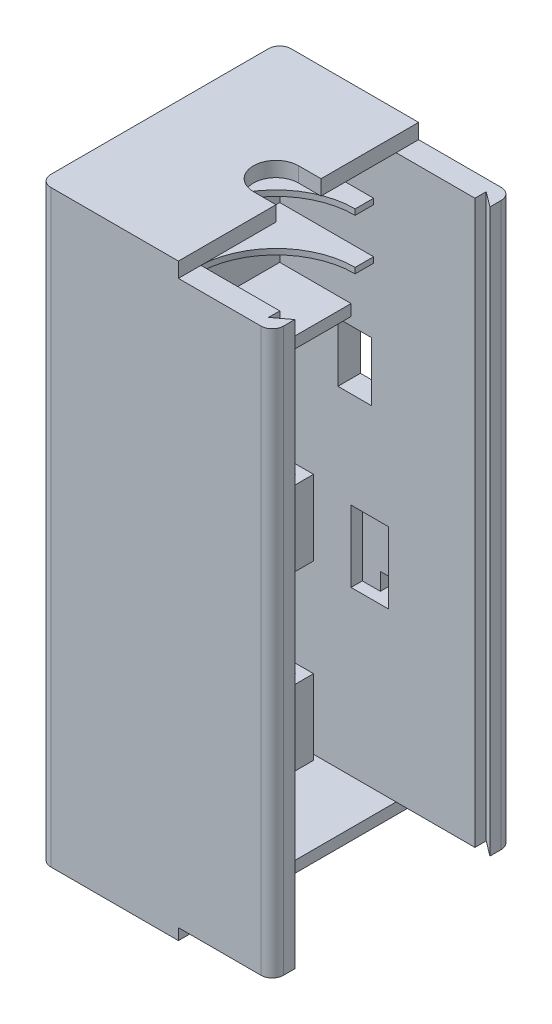
SolidWorks part; units mm, degrees
ref_plane "Alzado" through (0, 0, 0) normal (0, 0, 1) x (1, 0, 0)
ref_plane "Planta" through (0, 0, 0) normal (0, 1, 0) x (1, 0, 0)
ref_plane "Vista lateral" through (0, 0, 0) normal (1, 0, 0) x (0, 0, -1)
sketch "Croquis1" plane through (0, 0, 0) normal (0, 1, 0) x (1, 0, 0)
  line L1 (0, 0) -> (31, 0)
  line L2 (0, 0) -> (0, 32)
  line L3 (0, 32) -> (31, 32)
  line L4 (31, 0) -> (31, 32)
  dimension "D1" = 32
  dimension "D2" = 31
extrude "Saliente-Extruir1" add sketch "Croquis1" along normal blind 78.4
sketch "Croquis2" plane through (31, 0, 0) normal (1, 0, 0) x (0, 0, -1)
  line L1 (3, 76.4) -> (29, 76.4)
  line L2 (3, 1.5) -> (3, 54.5)
  line L3 (3, 1.5) -> (29, 1.5)
  line L4 (16, 78.4) -> (16, 0) construction
  line L5 (0, 78.4) -> (0, 0) construction
  line L6 (0, 78.4) -> (32, 78.4) construction
  line L7 (0, 0) -> (32, 0) construction
  line L9 (3, 56) -> (29, 56) construction
  line L10 (3, 56) -> (29, 56)
  line L11 (3, 54.5) -> (29, 54.5)
  line L24 (29, 76.4) -> (29, 56)
  line L25 (3, 76.4) -> (3, 56)
  line L41 (29, 1.5) -> (29, 54.5)
  point P31 (16, 1.5)
  point P32 (16, 76.4)
  dimension "D1" = 3
  dimension "D2" = 1.5
  dimension "D3" = 53
  dimension "D4" = 1.5
  dimension "D5" = 20.4
extrude "Cortar-Extruir1" cut sketch "Croquis2" against normal offset from surface (26 mm away) 3 from offset 2 up to face at (0, 39.2, -16) offset against normal yes
sketch "Croquis3" plane through (0, 78.4, 0) normal (0, 1, 0) x (1, 0, 0)
  line L0 (0, 32) -> (31, 0) construction
  line L1 (0, 0) -> (31, 32) construction
  line L2 (15.5, 16) -> (15.5, 32) construction
  line L3 (31, 32) -> (0, 32) construction
  circle A0 centre (15.5, 16) radius 3
  dimension "D1" = 6
extrude "Cortar-Extruir2" cut sketch "Croquis3" against normal blind 5
sketch "Croquis4" plane through (31, 0, 0) normal (1, 0, 0) x (0, 0, -1)
  line L0 (0, 78.4) -> (32, 78.4) construction
  line L1 (3, 76.9) -> (29, 76.9)
  line L2 (3, 76.9) -> (3, 1.5)
  line L3 (3, 1.5) -> (29, 1.5)
  line L4 (29, 76.9) -> (29, 1.5)
  line L5 (32, 78.4) -> (32, 0) construction
  line L6 (0, 78.4) -> (0, 0) construction
  line L7 (0, 0) -> (32, 0) construction
  dimension "D1" = 1.5
  dimension "D2" = 3
  dimension "D3" = 3
  dimension "D4" = 1.5
extrude "Cortar-Extruir3" cut sketch "Croquis4" against normal blind 2
sketch "Croquis5" plane through (0, 54.5, 0) normal (0, -1, 0) x (1, 0, 0)
  line L0 (0, 0) -> (31, -32) construction
  line L1 (31, 0) -> (0, -32) construction
  line L3 (12.5, -16) -> (15.5, -16) construction
  line L5 (12.5, -29) -> (12.5, -3)
  line L6 (3, -29) -> (29, -29) construction
  line L7 (3, -3) -> (29, -3) construction
  line L10 (12.5, -3) -> (34.7476, -3)
  line L11 (34.7476, -3) -> (34.7476, -29)
  line L12 (34.7476, -29) -> (12.5, -29)
  arc A0 (15.5, -13) -> (15.5, -19) centre (15.5, -16) ccw construction
  dimension "D1" = 6
extrude "Cortar-Extruir4" cut sketch "Croquis5" against normal blind 19
sketch "Croquis6" plane through (0, 54.5, 0) normal (0, -1, 0) x (1, 0, 0)
  line L0 (3, -3) -> (31, -3) construction
  line L1 (3, -29) -> (3, -3) construction
  line L2 (3, -17.1) -> (3, -18.3)
  line L3 (3, -18.3) -> (18.2, -18.3)
  line L4 (26, -16) -> (31, -16) construction
  line L5 (17, -17.1) -> (3, -17.1)
  line L7 (3, -3) -> (12.5, -3) construction
  line L8 (31, 0) -> (31, -32) construction
  line L9 (0, 0) -> (31, -32) construction
  line L10 (31, 0) -> (0, -32) construction
  line L12 (17, -3) -> (18.2, -3)
  line L13 (17, -3) -> (17, -17.1)
  line L15 (18.2, -3) -> (18.2, -18.3)
  circle A1 centre (10, -10) radius 7 construction
  circle A2 centre (15.5, -16) radius 1 construction
  circle A3 centre (15.5, -16) radius 10.5 construction
  dimension "D3" = 14
  dimension "D4" = 2
  dimension "D5" = 21
  dimension "D1" = 1.2
  dimension "D2" = 14.1
sketch "Croquis9" plane through (0, 0, -29) normal (0, 0, 1) x (1, 0, 0)
  line L0 (3, 1.5) -> (3, 54.5) construction
  line L12 (31, 38.0162) -> (3, 38.0162) construction
  line L13 (31, 78.4) -> (31, 0) construction
  circle A2 centre (17, 38.0162) radius 5
  dimension "D1" = 10
ref_axis "Eje1" through (15.5, -7.3463, -16) along (0, 1, 0)
sketch "Croquis11" plane through (0, 76.4, 0) normal (0, -1, 0) x (1, 0, 0)
  line L0 (15.5, -3) -> (15.5, -5.45)
  line L1 (3, -3) -> (31, -3) construction
  line L2 (15.5, -3) -> (3, -3)
  line L3 (3, -3) -> (3, -29)
  line L4 (3, -29) -> (15.5, -29)
  line L5 (3, -29) -> (31, -29) construction
  line L6 (15.5, -29) -> (15.5, -26.55)
  line L7 (0, 0) -> (31, -32) construction
  line L8 (31, 0) -> (0, -32) construction
  arc A0 (15.5, -5.45) -> (15.5, -26.55) centre (15.5, -16) ccw
  circle A1 centre (15.5, -16) radius 3 construction
  dimension "D1" = 21.1
  dimension "D3" = 6
  dimension "D2" = 12.5
extrude "Saliente-Extruir4" add sketch "Croquis11" along normal blind 0.75 from offset 6.75
pattern_linear "MatrizL1" count 2 spacing 6.75 along (0, -1, 0) of "Saliente-Extruir4"
extrude "Saliente-Extruir5" add sketch "Croquis6" along normal blind 10 from offset 10
pattern_linear "MatrizL2" count 2 spacing 23 along (0, -1, 0) of "Saliente-Extruir5"
sketch "Croquis14" plane through (0, 76.4, 0) normal (0, -1, 0) x (1, 0, 0)
  line L1 (18.5, 0) -> (31, 0)
  line L2 (18.5, 0) -> (18.5, -13)
  line L3 (18.5, -32) -> (31, -32)
  line L4 (31, 0) -> (31, -32)
  line L5 (15.5, -13) -> (18.5, -13)
  line L7 (15.5, -13) -> (15.5, -19)
  line L8 (15.5, -19) -> (18.5, -19)
  line L9 (18.5, -19) -> (18.5, -32)
  line L10 (0, 0) -> (31, 0) construction
  circle A0 centre (15.5, -16) radius 3 construction
  circle A1 centre (15.5, -16) radius 3 construction
  dimension "D1" = 6
  dimension "D2" = 3
extrude "Cortar-Extruir8" cut sketch "Croquis14" against normal blind 10
sketch "Croquis15" plane through (0, 1.5, 0) normal (0, 1, 0) x (1, 0, 0)
  line L0 (18.5, 0) -> (18.5, 13) construction
  line L1 (18.5, 32) -> (31, 32)
  line L2 (18.5, 32) -> (18.5, 0)
  line L3 (18.5, 0) -> (31, 0)
  line L4 (31, 32) -> (31, 0)
  line L5 (18.5, 32) -> (31, 32) construction
extrude "Cortar-Extruir11" cut sketch "Croquis15" against normal blind 10
sketch "Croquis16" plane through (0, 0, 0) normal (-1, 0, 0) x (0, 0, 1)
  line L0 (-3, 54.5) -> (-29, 54.5) construction
  line L1 (-3, 1.5) -> (-17.1, 1.5)
  line L2 (-3, 1.5) -> (-3, 54.5)
  line L3 (-3, 54.5) -> (-17.1, 54.5)
  line L4 (-17.1, 1.5) -> (-17.1, 54.5)
  line L5 (-17.1, 34.5) -> (-17.1, 44.5) construction
extrude "Cortar-Extruir12" cut sketch "Croquis16" against normal blind 10
sketch "Croquis17" plane through (0, 0, 0) normal (0, -1, 0) x (1, 0, 0)
  line L0 (0, -17.1) -> (2, -19.1)
  line L1 (2, -19.1) -> (2, -1)
  line L2 (2, -1) -> (0, -3)
  line L3 (0, -3) -> (0, -17.1)
  dimension "D1" = 45
  dimension "D2" = 2
  dimension "D3" = 45
extrude "Cortar-Extruir13" cut sketch "Croquis17" against normal up to surface (54.5 mm away) up to face at (3.3333, 54.5, -16.3667)
sketch "Croquis18" plane through (0, 76.4, 0) normal (0, 1, 0) x (1, 0, 0)
  line L0 (31, 29) -> (29, 30.5)
  line L1 (29, 30.5) -> (29, 29)
  line L3 (29, 29) -> (31, 29)
  line L4 (0, 16) -> (33.2746, 16) construction
  line L5 (0, 32) -> (0, 0) construction
  line L6 (29, 3) -> (31, 3)
  line L7 (29, 1.5) -> (29, 3)
  line L8 (31, 3) -> (29, 1.5)
  dimension "D2" = 2
  dimension "D3" = 29
extrude "Cortar-Extruir14" cut sketch "Croquis18" against normal blind 95
sketch "Croquis19" plane through (0, 0, -32) normal (0, 0, -1) x (-1, 0, 0)
  line L0 (-31, 53.425) -> (0, 53.425) construction
  line L1 (-15.25, 53.425) -> (-10.75, 53.425)
  line L2 (-15.25, 53.425) -> (-15.25, 45.575)
  line L3 (-15.25, 45.575) -> (-10.75, 45.575)
  line L4 (-10.75, 53.425) -> (-10.75, 45.575)
  line L5 (-31, 76.4) -> (-31, 1.5) construction
  line L6 (0, 78.4) -> (0, 0) construction
  line L8 (-17.5, 32.75) -> (-12.5, 32.75)
  line L9 (-17.5, 32.75) -> (-17.5, 23.25)
  line L10 (-17.5, 23.25) -> (-12.5, 23.25)
  line L11 (-12.5, 32.75) -> (-12.5, 23.25)
  line L12 (-6.9738, 34.5) -> (-6.9738, 21.5) construction
  line L13 (-3, 34.5) -> (-18.2, 34.5) construction
  line L14 (-3, 21.5) -> (-18.2, 21.5) construction
  line L15 (-12.5, 28) -> (-6.9738, 28) construction
  line L16 (-5.9745, 54.5) -> (-5.9745, 44.5) construction
  line L17 (-3, 54.5) -> (-12.5, 54.5) construction
  line L18 (-3, 44.5) -> (-18.2, 44.5) construction
  line L19 (-10.75, 49.5) -> (-5.9745, 49.5) construction
  point P10 (-15, 32.75)
  point P16 (-13, 53.425)
  dimension "D1" = 7.85
  dimension "D2" = 4.5
  dimension "D3" = 5
  dimension "D4" = 9.5
  dimension "D5" = 13
  dimension "D6" = 15
extrude "Cortar-Extruir15" cut sketch "Croquis19" along normal offset from surface (1.5 mm away) 1.5 from surface up to face at (17, 39.075, -32) starting at face at (10.7778, 54.55, -29)
sketch "Croquis21" plane through (0, 0, -32) normal (0, 0, -1) x (-1, 0, 0)
  line L1 (-15.25, 53.425) -> (-10.75, 53.425)
  line L2 (-15.25, 53.425) -> (-15.25, 45.575)
  line L3 (-15.25, 45.575) -> (-10.75, 45.575)
  line L4 (-10.75, 53.425) -> (-10.75, 45.575)
  line L5 (-17.5, 23.25) -> (-14.9, 23.25)
  line L6 (-17.5, 23.25) -> (-17.5, 25.55)
  line L7 (-17.5, 25.55) -> (-14.9, 25.55)
  line L8 (-14.9, 23.25) -> (-14.9, 25.55)
  dimension "D1" = 2.3
  dimension "D2" = 2.6
extrude "Cortar-Extruir16" cut sketch "Croquis21" against normal blind 1.5
fillet "Redondeo1" radius 1.5 4 edges at (0, 39.2, 0) (0, 39.2, -32) (31, 38.95, -32) (31, 38.95, 0)
sketch "Croquis22" plane through (0, 0, -32) normal (0, 0, -1) x (-1, 0, 0)
  line L0 (-15.25, 52.1781) -> (-29.5, 52.1781) construction
  line L1 (-29.5, 76.4) -> (-29.5, 1.5) construction
  line L2 (-15.25, 44.5117) -> (-29.5, 44.5117) construction
  line L3 (-17.5, 22.6086) -> (-29.5, 22.6086) construction
  line L4 (-14.9, 22.6086) -> (-1.5, 22.6086) construction
  line L5 (-1.5, 0) -> (-1.5, 78.4) construction
  line L6 (-15.25, 53.425) -> (-15.25, 45.575) construction
  text T0 "ON  " font "Arial" height in points 10
  text T1 "OFF  " font "Arial" height in points 10
  text T2 "-   " font "Arial" height in points 18
  text T3 "+   " font "Arial" height in points 18
extrude "Cortar-Extruir17" cut sketch "Croquis22" against normal blind 1.5
